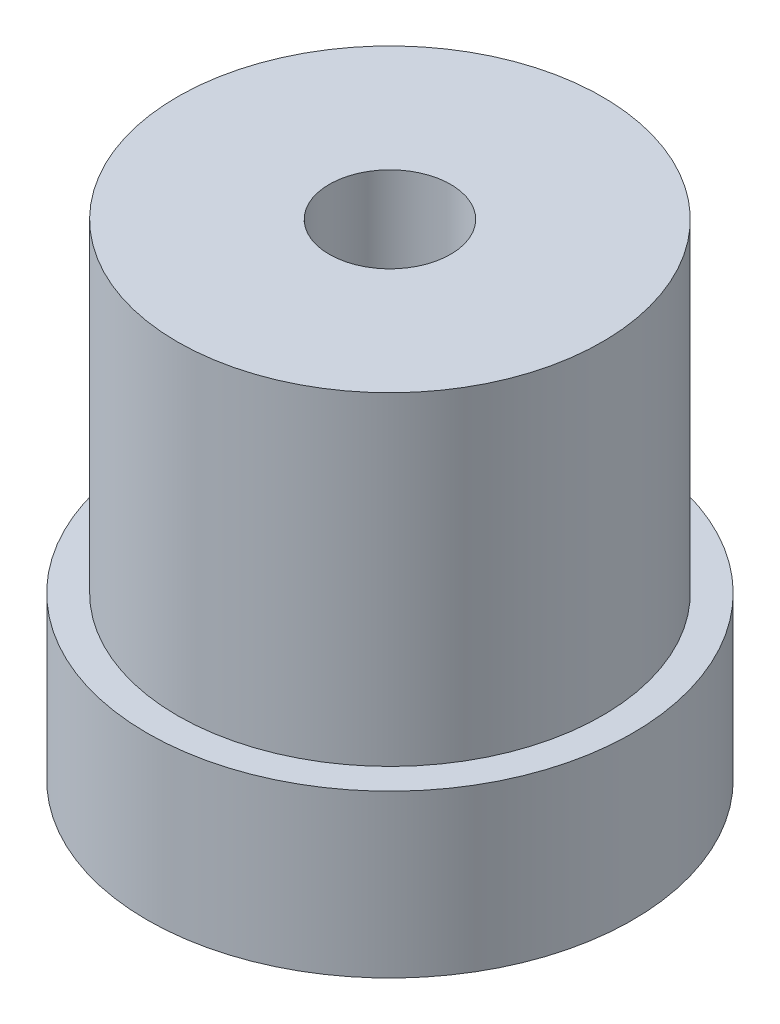
SolidWorks part; units mm, degrees
material "6061 Alloy"
ref_plane "Front Plane" through (0, 0, 0) normal (0, 0, 1) x (1, 0, 0)
ref_plane "Top Plane" through (0, 0, 0) normal (0, 1, 0) x (1, 0, 0)
ref_plane "Right Plane" through (0, 0, 0) normal (1, 0, 0) x (0, 0, -1)
sketch "Sketch1" plane through (0, 0, 0) normal (0, 1, 0) x (1, 0, 0)
  circle A0 centre (0, 0) radius 76.2
  dimension "D1" = 152.4
extrude "Boss-Extrude1" add sketch "Sketch1" along normal blind 50.8
sketch "Sketch2" plane through (0, 50.8, 0) normal (0, 1, 0) x (1, 0, 0)
  circle A0 centre (0, 0) radius 66.675
  dimension "D1" = 133.35
extrude "Boss-Extrude2" add sketch "Sketch2" along normal blind 101.6
sketch "Sketch3" plane through (0, 152.4, 0) normal (0, 1, 0) x (1, 0, 0)
  circle A0 centre (0, 0) radius 19.05
extrude "Cut-Extrude1" cut sketch "Sketch3" against normal blind 38.1
ref_point "point_to_put_arm_on_truck"
ref_axis "axis_base_frame" through (0, 648.2721, 0) along (0, -1, 0)
ref_plane "plane_to_put_arm_on_truck" through (0, 0, 0) normal (0, -1, 0) x (-1, 0, 0)
sketch "Sketch4" plane through (0, 0, 0) normal (0, -1, 0) x (1, 0, 0)
  circle A0 centre (0, 0) radius 12.7
